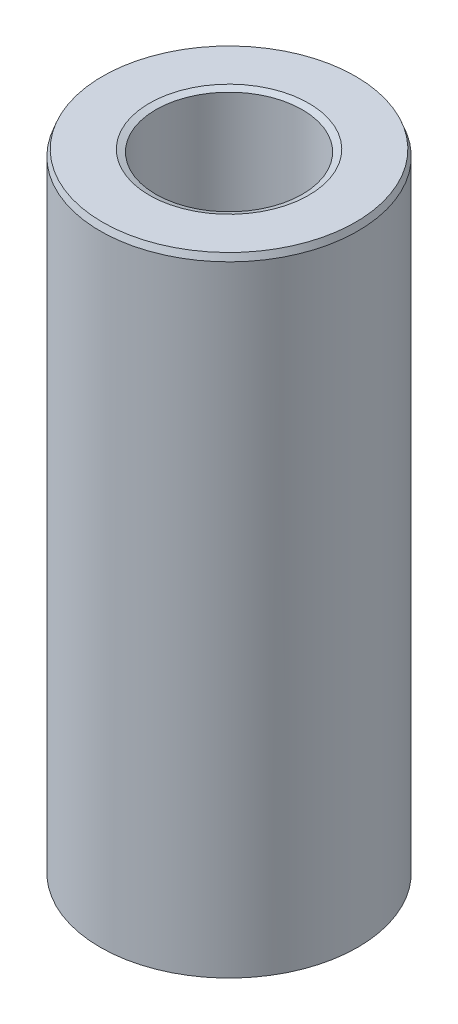
SolidWorks part; units mm, degrees
ref_plane "Front Plane" through (0, 0, 0) normal (0, 0, 1) x (1, 0, 0)
ref_plane "Top Plane" through (0, 0, 0) normal (0, 1, 0) x (1, 0, 0)
ref_plane "Right Plane" through (0, 0, 0) normal (1, 0, 0) x (0, 0, -1)
sketch "Sketch1" plane through (0, 0, 0) normal (0, 1, 0) x (1, 0, 0)
  circle A0 centre (0, 0) radius 25
  dimension "SLEEVE_OD" = 50
extrude "Boss-Extrude1" add sketch "Sketch1" along normal blind 122.0527
sketch "Sketch2" plane through (0, 0, 0) normal (0, 1, 0) x (1, 0, 0)
  circle A0 centre (0, 0) radius 14.2198
  dimension "BORE_D" = 28.4395
extrude "Cut-Extrude1" cut sketch "Sketch2" along normal through all
chamfer "Chamfer1" distance 1.248 angle 20.316 4 edges at (0, 122.0527, 14.2198) (0, 0, 14.2198) (0, 0, 25) (0, 122.0527, 25) first distance on face at (0, 122.0527, 14.2198) first distance on face at (0, 0, 14.2198) first distance on face at (0, 122.0527, 25)
